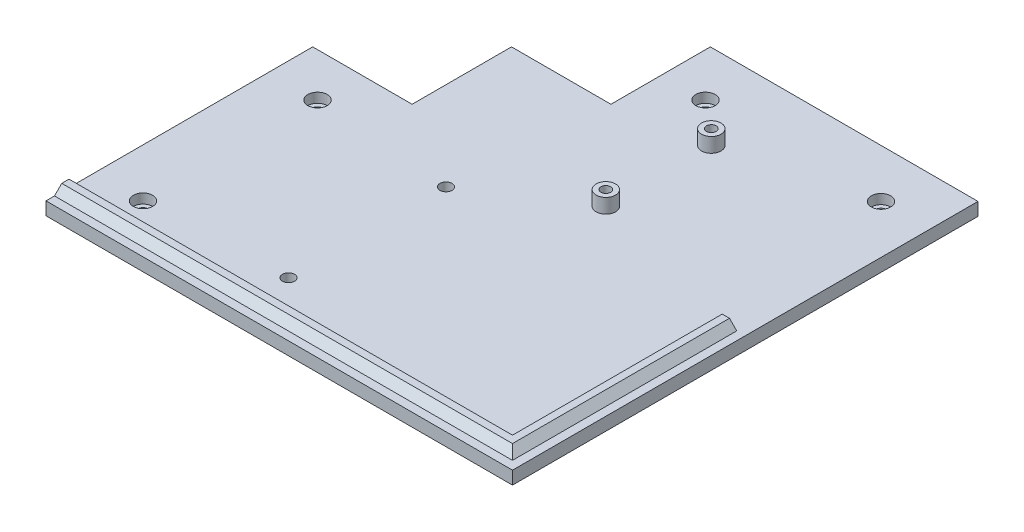
SolidWorks part; units mm, degrees
ref_plane "Front Plane" through (0, 0, 0) normal (0, 0, 1) x (1, 0, 0)
ref_plane "Top Plane" through (0, 0, 0) normal (0, 1, 0) x (1, 0, 0)
ref_plane "Right Plane" through (0, 0, 0) normal (1, 0, 0) x (0, 0, -1)
sketch "Sketch1" plane through (0, 0, 0) normal (0, 1, 0) x (1, 0, 0)
  line L1 (-96.2, 96) -> (96.2, 96)
  line L2 (-96.2, 96) -> (-96.2, -96)
  line L3 (-96.2, -96) -> (96.2, -96)
  line L4 (96.2, 96) -> (96.2, -96)
  line L5 (-96.2, 96) -> (96.2, -96) construction
  line L6 (-96.2, -96) -> (96.2, 96) construction
  point P0 (0, 0)
  dimension "D1" = 192
  dimension "D2" = 192.4
extrude "Boss-Extrude1" add sketch "Sketch1" along normal blind 6.35
sketch "Sketch2" plane through (0, 6.35, 0) normal (0, 1, 0) x (1, 0, 0)
  line L1 (-96.2, 96) -> (-55.2, 96)
  line L2 (-96.2, 96) -> (-96.2, 55)
  line L3 (-96.2, 55) -> (-55.2, 55) construction
  line L4 (-55.2, 96) -> (-55.2, 55) construction
  line L5 (-96.2, 55) -> (-55.2, 55)
  line L6 (-96.2, 55) -> (-96.2, 14)
  line L7 (-96.2, 14) -> (-55.2, 14)
  line L8 (-55.2, 55) -> (-55.2, 14)
  line L9 (-55.2, 96) -> (-14.2, 96)
  line L10 (-55.2, 96) -> (-55.2, 55)
  line L11 (-55.2, 55) -> (-14.2, 55)
  line L12 (-14.2, 96) -> (-14.2, 55)
  line M14 (96.2, 96) -> (-96.2, 96)
  line M15 (-96.2, 96) -> (-96.2, -96)
  dimension "D1" = 41
extrude "Cut-Extrude1" cut sketch "Sketch2" against normal up to next contours L8 L5 L7 M15 | L10 L5 M14 M15 | L12 L10 L11 M14 region at (-75.7, 6.35, -75.5) region at (-34.7, 6.35, -75.5) region at (-75.7, 6.35, -34.5)
sketch "Sketch3" plane through (0, 6.35, 0) normal (0, 1, 0) x (1, 0, 0)
  line L0 (-96.2, 76) -> (96.2, 76) construction
  line L1 (-96.2, 96) -> (-56.2, 96) construction
  line L2 (-96.2, 96) -> (-96.2, -96) construction
  line L3 (-96.2, -96) -> (-56.2, -96) construction
  line L4 (96.2, 96) -> (-96.2, 96)
  line L5 (96.2, -96) -> (96.2, 96)
  line L6 (-96.2, -96) -> (96.2, -96)
  line L7 (-96.2, 96) -> (-96.2, -96)
  line L8 (96.2, 96) -> (-96.2, 96) construction
  line L9 (96.2, -96) -> (96.2, 96) construction
  line L10 (-96.2, -96) -> (96.2, -96) construction
  line L11 (-96.2, 96) -> (-96.2, -96) construction
  line L12 (-56.2, 96) -> (-56.2, -96) construction
  line L13 (-96.2, 96) -> (96.2, 96) construction
  line L14 (-96.2, 96) -> (-96.2, 56) construction
  line L15 (-96.2, 56) -> (96.2, 56) construction
  line L16 (96.2, 96) -> (96.2, 56) construction
  line L17 (-76.2, 96) -> (-76.2, -96) construction
  point P20 (-76.2, -4)
  point P22 (-76.2, -76)
  point P24 (3.8, 76)
  point P26 (76.2, 76)
  dimension "D2" = 40
  dimension "D3" = 40
  dimension "D4" = 20
  dimension "D5" = 60
  dimension "D6" = 60
  dimension "D7" = 20
  dimension "D8" = 20
  dimension "D1" = 0
hole_wizard "CBORE for M4 SHCS1" positions "Sketch3" profile "Sketch4" counterbore size "M4" standard "ANSI Metric" end condition up to next
sketch "Sketch4" plane through (76.2, 6.35, -76) normal (1, 0, 0) x (0, 0, 1)
  line L0 (0, 0) -> (0, 6.35)
  line L1 (0, 6.35) -> (2.25, 6.35)
  line L3 (2.25, 6.35) -> (2.25, 4)
  line L4 (2.25, 4) -> (4, 4)
  line L5 (4, 4) -> (4, 0)
  line L7 (4, 0) -> (0, 0)
  line L11 (0, -6.35) -> (0, 107.95) construction
  dimension "Thru Hole Dia." = 4.5
  dimension "Thru Hole Depth" = 6.35
  dimension "C'Bore Dia." = 8
  dimension "C'Bore Depth" = 4
mirror "Mirror1" [suppressed] of bodies 105
delete or keep bodies "Body-Delete/Keep 1" [suppressed] type delete bodies bodies 105
mirror "Mirror2" [suppressed] of bodies 108
delete or keep bodies "Body-Delete/Keep 2" [suppressed] type delete bodies bodies 108
sketch "Sketch5" plane through (0, 6.35, 0) normal (0, 1, 0) x (1, 0, 0)
  line L0 (-18.7, -8.525) -> (-18.7, -73.475) construction
  line L1 (-56.2, -4.375) -> (18.8, -4.375) construction
  line L2 (-56.2, -4.375) -> (-56.2, -77.625) construction
  line L3 (-56.2, -77.625) -> (18.8, -77.625) construction
  line L4 (18.8, -4.375) -> (18.8, -77.625) construction
  line L5 (-96.2, -41) -> (96.2, -41) construction
  line L6 (-96.2, 14) -> (-96.2, -96) construction
  line L7 (96.2, -96) -> (96.2, 96) construction
  line L8 (-56.2, -41) -> (18.8, -41) construction
  circle A0 centre (-18.7, -8.525) radius 2.5
  circle A1 centre (-18.7, -73.475) radius 2.5
  point P12 (-18.7, -41)
  point P15 (-18.7, -41)
  dimension "D4" = 5
  dimension "D1" = 73.25
  dimension "D2" = 75
  dimension "D3" = 40
  dimension "D5" = 64.95
extrude "Cut-Extrude2" cut sketch "Sketch5" against normal blind 6
sketch "Sketch6" plane through (0, 0.35, 0) normal (0, 1, 0) x (1, 0, 0)
  circle A0 centre (-18.7, -8.525) radius 2.25
  circle A1 centre (-18.7, -73.475) radius 2.25
  dimension "D1" = 4.5
extrude "Cut-Extrude3" cut sketch "Sketch6" against normal up to next
sketch "Sketch7" plane through (0, 6.35, 0) normal (0, 1, 0) x (1, 0, 0)
  line L0 (96.2, -96) -> (96.2, 96) construction
  line L1 (21.2, 61) -> (171.2, 61) construction
  line L2 (21.2, 61) -> (21.2, 17.5) construction
  line L3 (21.2, 17.5) -> (171.2, 17.5) construction
  line L4 (171.2, 61) -> (171.2, 17.5) construction
  line L5 (21.2, 61) -> (171.2, 17.5) construction
  line L6 (21.2, 17.5) -> (171.2, 61) construction
  line L7 (96.2, 96) -> (-14.2, 96) construction
  circle A0 centre (21.2, 61) radius 1.75
  circle A1 centre (21.2, 17.5) radius 1.75
  point P0 (96.2, 39.25)
  dimension "D4" = 3.5
  dimension "D1" = 43.5
  dimension "D2" = 150
  dimension "D3" = 35
extrude "Cut-Extrude4" cut sketch "Sketch7" against normal up to next
sketch "Sketch11" plane through (0, 6.35, 0) normal (0, 1, 0) x (1, 0, 0)
  circle A0 centre (21.2, 17.5) radius 1.75 construction
  circle A1 centre (21.2, 61) radius 1.75 construction
  circle A2 centre (21.2, 17.5) radius 1.75
  circle A3 centre (21.2, 61) radius 1.75
  circle A4 centre (21.2, 61) radius 4
  circle A5 centre (21.2, 17.5) radius 4
  dimension "D1" = 8
extrude "Boss-Extrude2" add sketch "Sketch11" along normal blind 6
sketch "Sketch8" plane through (0, 12.35, 0) normal (0, 1, 0) x (1, 0, 0)
  circle A0 centre (21.2, 61) radius 2
  circle A1 centre (21.2, 17.5) radius 2
  dimension "D1" = 4
extrude "Cut-Extrude5" cut sketch "Sketch8" against normal blind 5
sketch "Sketch9" plane through (0, 6.35, 0) normal (0, 1, 0) x (1, 0, 0)
  line L2 (0, 0) -> (96.2, 0) construction
  line L3 (96.2, -96) -> (96.2, 96) construction
  line L4 (-96.2, -88) -> (88.2, -88)
  line L5 (88.2, -88) -> (88.2, 96)
  line L6 (-96.2, -88) -> (88.2, -88)
  line L7 (88.2, -88) -> (88.2, 0)
  dimension "D1" = 8
extrude "Extrude-Thin1" add sketch "Sketch9" along normal blind 3 thin thin type mid plane wall 3
chamfer "Chamfer1" distance 3 angle 45 4 edges at (-4.75, 6.35, 86.5) (86.7, 6.35, 43.25) (-3.25, 6.35, 89.5) (89.7, 6.35, 44.75)
chamfer "Chamfer2" distance 1 angle 45 2 edges at (0, 0, 96) (96.2, 0, 0)
mirror "Mirror3" [suppressed] of bodies 115 113
delete or keep bodies "Body-Delete/Keep 4" [suppressed] type delete bodies bodies 115
equation "\"D2@Sketch1\"=384.8/2"
